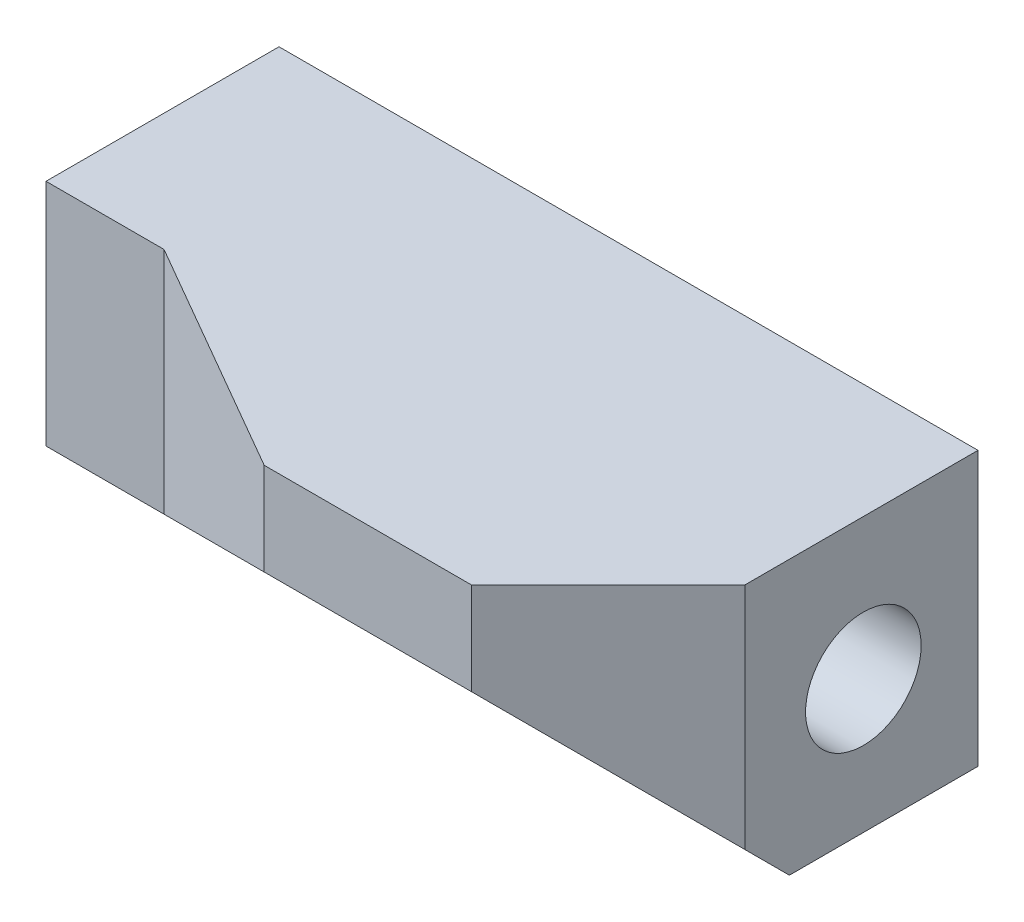
SolidWorks part; units mm, degrees
ref_plane "Front Plane" through (0, 0, 0) normal (1, 0, 0) x (0, 1, 0)
ref_plane "Top Plane" through (0, 0, 0) normal (0, 0, 1) x (0, 1, 0)
ref_plane "Right Plane" through (0, 0, 0) normal (0, 1, 0) x (-1, 0, 0)
sketch "Sketch1" plane through (0, 0, 0) normal (1, 0, 0) x (0, 1, 0)
  line L0 (0, 0) -> (0, 50.8)
  line L1 (0, 50.8) -> (-12.7, 50.8)
  line L2 (-12.7, 50.8) -> (-56.896, 6.604)
  line L3 (-56.896, 6.604) -> (-56.896, 0)
  line L4 (-56.896, 0) -> (0, 0)
  circle A0 centre (-19.304, 15.748) radius 7.9375
  point P10 (-4.1699, -13.7314)
  dimension "D1" = 15.875
  dimension "D2" = 50.8
  dimension "D3" = 56.896
  dimension "D4" = 12.7
  dimension "D5" = 45
  dimension "D6" = 15.748
  dimension "D7" = 19.304
extrude "Boss-Extrude1" add sketch "Sketch1" against normal blind 96.012 contours L3 L4 L0 L1 L2 A0 | A0 region at (0, -28.448, 0.7627) region at (0, -19.304, 15.748)
extrude "Cut-Extrude1" cut sketch "Sketch1<3>" against normal blind 31.75 contours A0
sketch "Sketch1<3>" plane through (0, 0, 0) normal (1, 0, 0) x (0, 1, 0) same geometry as "Sketch1"
sketch "Sketch3" plane through (0, 0, 0) normal (0, 0, -1) x (1, 0, 0)
  line L0 (0, 37.592) -> (-25.4, 37.592)
  line L1 (0, 56.896) -> (0, 0) construction
  line L2 (-25.4, 37.592) -> (-25.4, 56.896)
  line L3 (-96.012, 56.896) -> (0, 56.896) construction
  line L4 (-70.612, 56.896) -> (-70.612, 43.18)
  line L5 (-70.612, 43.18) -> (-41.656, 43.18)
  line L6 (-41.656, 43.18) -> (-41.656, 56.896)
  line L7 (-96.012, 56.896) -> (-96.012, 0) construction
  line M5 (0, 0) -> (0, 56.896)
  line M6 (0, 56.896) -> (-96.012, 56.896)
  dimension "D1" = 19.304
  dimension "D2" = 25.4
  dimension "D3" = 28.956
  dimension "D4" = 25.4
  dimension "D5" = 13.716
extrude "Cut-Extrude2" cut sketch "Sketch3" against normal through all contours L5 L6 L4 M6 | L2 L0 M5 M6 region at (-56.134, -50.038, 0) region at (-12.7, -47.244, 0)
sketch "Sketch4" plane through (0, 0, 0) normal (0, 1, 0) x (-1, 0, 0)
  line L0 (47.244, 50.8) -> (79.7996, 32.004)
  line L1 (96.012, 50.8) -> (0, 50.8) construction
  line L2 (79.7996, 32.004) -> (96.012, 32.004)
  line L3 (96.012, 0) -> (96.012, 50.8) construction
  line L4 (18.796, 50.8) -> (0, 32.004)
  line L5 (0, 0) -> (0, 50.8) construction
  line M4 (0, 50.8) -> (0, 0)
  line M6 (96.012, 0) -> (96.012, 50.8)
  line M7 (96.012, 50.8) -> (0, 50.8)
  dimension "D1" = 18.796
  dimension "D2" = 30
  dimension "D3" = 28.448
  dimension "D4" = 18.796
  dimension "D5" = 45
extrude "Cut-Extrude3" cut sketch "Sketch4" against normal through all contours L4 M7 M4 | L0 L2 M6 M7 region at (-78.4077, 0, 42.9715) region at (-6.2653, 0, 44.5347)
